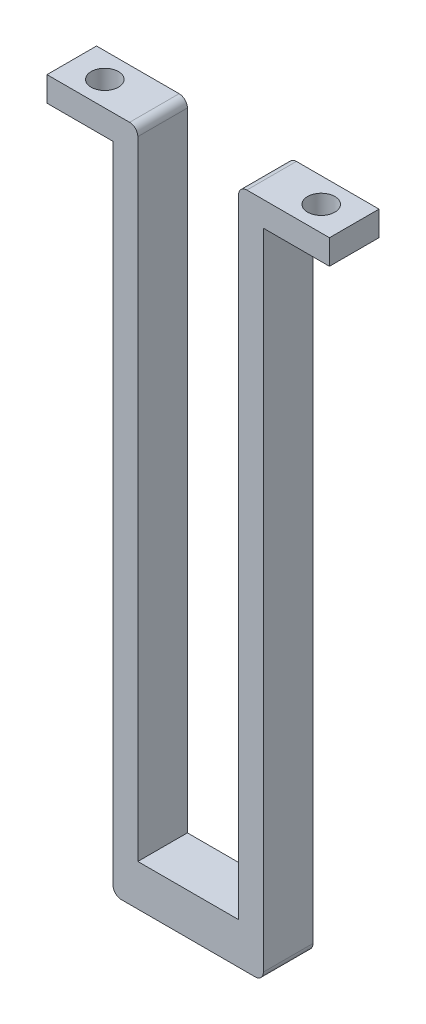
SolidWorks part; units mm, degrees
ref_plane "Front Plane" through (0, 0, 0) normal (0, 0, 1) x (1, 0, 0)
ref_plane "Top Plane" through (0, 0, 0) normal (0, 1, 0) x (1, 0, 0)
ref_plane "Right Plane" through (0, 0, 0) normal (1, 0, 0) x (0, 0, -1)
sketch "Sketch6" plane through (0, 0, 0) normal (0, 0, 1) x (1, 0, 0)
  line L0 (-6.1, 0) -> (6.1, 0)
  line L1 (6.1, 0) -> (6.1, 77)
  line L2 (6.1, 77) -> (17.1, 77)
  line L3 (17.1, 77) -> (17.1, 74)
  line L4 (17.1, 74) -> (9.1, 74)
  line L5 (9.1, 74) -> (9.1, -5)
  line L6 (9.1, -5) -> (-9.1, -5)
  line L7 (0, 4.2064) -> (0, -6.4903) construction
  line L8 (-9.1, 74) -> (-9.1, -5)
  line L9 (-17.1, 74) -> (-9.1, 74)
  line L10 (-17.1, 77) -> (-17.1, 74)
  line L11 (-6.1, 77) -> (-17.1, 77)
  line L12 (-6.1, 0) -> (-6.1, 77)
  point P12 (0, -5)
  point P17 (0, 0)
  dimension "D1" = 6.1
  dimension "D2" = 82
  dimension "D3" = 3
  dimension "D4" = 3
  dimension "D5" = 11
  dimension "D6" = 5
extrude "Boss-Extrude5" add sketch "Sketch6" along normal blind 6
sketch "Sketch7" plane through (0, 74, 0) normal (0, -1, 0) x (1, 0, 0)
  line L0 (-9.1, 6) -> (-9.1, 0) construction
  line L1 (9.1, 6) -> (9.1, 0) construction
  line L2 (-17.1, 6) -> (-9.1, 6) construction
  line L3 (9.1, 6) -> (17.1, 6) construction
  circle A0 centre (-13.1, 3) radius 1.65
  circle A1 centre (13.1, 3) radius 1.65
  dimension "D1" = 3.3
  dimension "D2" = 3.3
  dimension "D3" = 4
  dimension "D4" = 4
  dimension "D5" = 3
  dimension "D6" = 3
extrude "Cut-Extrude2" cut sketch "Sketch7" against normal up to surface (3 mm away) up to face at (-11.6, 77, 3)
fillet "Fillet1" radius 1 2 edges at (-6.1, 77, 3) (6.1, 77, 3)
fillet "Fillet2" radius 1 2 edges at (9.1, -5, 3) (-9.1, -5, 3)
equation "\"D2@Sketch7\"=\"D1@Sketch7\""
equation "\"D4@Sketch7\"=\"D3@Sketch7\""
